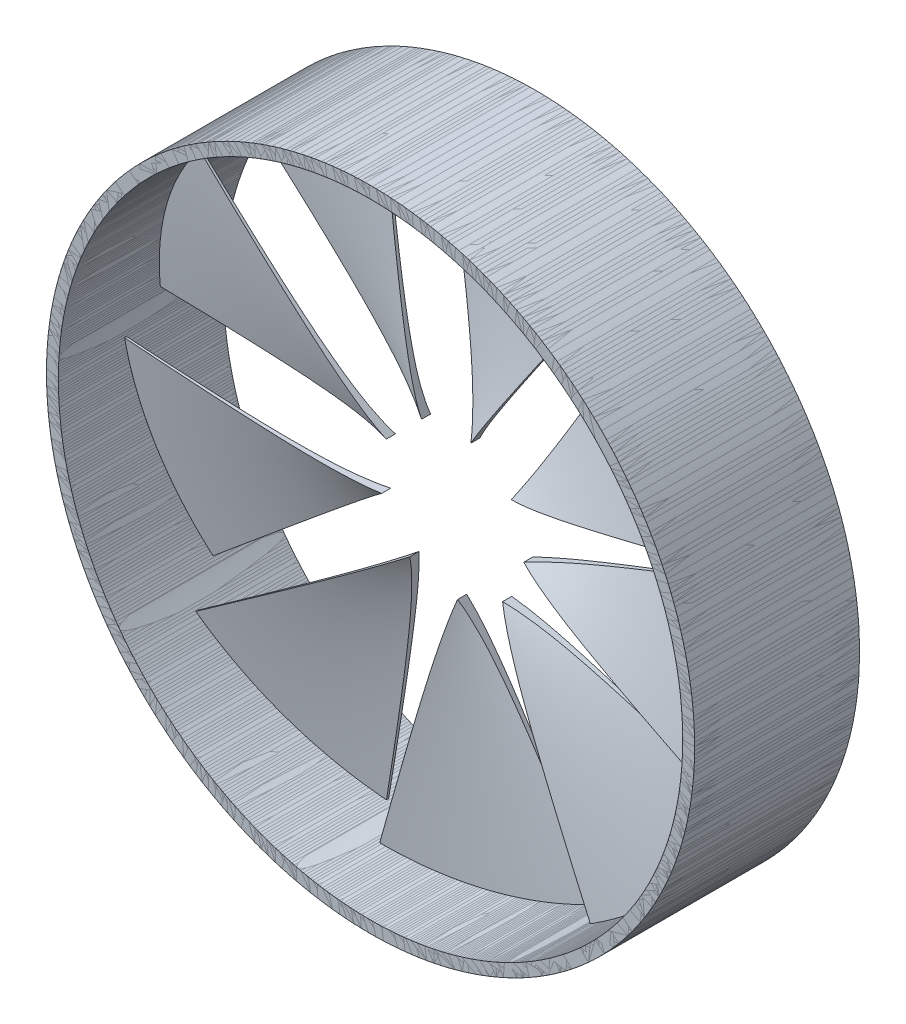
SolidWorks part; units mm, degrees
ref_plane "Front Plane" through (0, 0, 0) normal (0, 0, 1) x (1, 0, 0)
ref_plane "Top Plane" through (0, 0, 0) normal (0, 1, 0) x (1, 0, 0)
ref_plane "Right Plane" through (0, 0, 0) normal (1, 0, 0) x (0, 0, -1)
sketch "Sketch1" plane through (0, 0, 0) normal (0, 0, 1) x (1, 0, 0)
  circle A0 centre (0, 0) radius 137.5645
  dimension "D1" = 275.1291
curve "Helix/Spiral1" pitch 150 height 30 radius 137.5645 left hand yes centre (0, 0, 0) axis (0, 0, 1) start towards (-1, 0, 0)
sketch "Sketch2" plane through (0, 0, 0) normal (0, 0, 1) x (1, 0, 0)
  line L1 (-137.5645, 0) -> (-28.89, 0)
  line L2 (-137.5645, 0) -> (-137.5645, 5)
  line L3 (-137.5645, 5) -> (-28.89, 5)
  line L4 (-28.89, 0) -> (-28.89, 5)
  spline S0 degree 3 poles (-137.5645, 0) (-137.5646, 5.7586) (-136.8395, 17.2886) (-133.5938, 34.3006) (-128.2414, 50.7745) (-120.8664, 66.4468) (-111.5854, 81.0715) (-100.5445, 94.4176) (-87.9181, 106.2746) (-73.9046, 116.4558) (-58.7281, 124.7996) (-47.9865, 129.0522) (-42.5098, 130.8317) knots 0 0 0 0 0.1 0.2 0.3 0.4 0.5 0.6 0.7 0.8 0.9 1 1 1 1 construction
  dimension "D3" = 28.89
sweep "Sweep1" add profiles "Sketch2" path "Helix/Spiral1"
ref_plane "Plane1" through (0, 0, 0) normal (0, 0, 1) x (1, 0, 0)
sketch "Sketch9" plane through (0, 0, 0) normal (0, 0, 1) x (1, 0, 0)
  line L0 (-27.777, 13.1653) -> (-104.2926, 89.6808)
  line L1 (-27.777, 13.1653) -> (-136.917, 13.1653)
  arc A0 (-104.2926, 89.6808) -> (-136.917, 13.1653) centre (0, 0) ccw
  dimension "D2" = 45
  dimension "D1" = 137.5485
  dimension "D3" = 109.14
extrude "Cut-Extrude1" cut sketch "Sketch9" along normal blind 40 flip side to cut
sketch "Sketch10" plane through (0, 0, 0) normal (0, 0, 1) x (1, 0, 0)
  circle A0 centre (0, 0) radius 132.5645
  circle A1 centre (0, 0) radius 137.5645
  dimension "D2" = 265.1291
extrude "Boss-Extrude1" add sketch "Sketch10" along normal blind 45 and the other way blind 25
pattern_circular "CirPattern2" count 9 over 360 about axis through (0, 0, -25) along (0, 0, 1) reverse direction yes of bodies 103
equation "\"ThrusterDim\"=160.5mm"
equation "\"hatchHoleDiameter\"=600mm"
equation "\"hullThickness\"=177.1mm"
equation "\"gasketHullInterconnectWidth\"=100mm"
equation "\"collarThickness\"=20mm"
equation "\"hatchTunnelLength\"=200mm"
equation "\"oRingDiameter\"=2mm"
equation "\"boltPatternRadiusInterconnect\"=500mm"
equation "\"interconnectBoltDiameter\"=30mm"
equation "\"hatchShaftDiameter\"=20mm"
equation "\"hatchMinima\"=39.9mm"
equation "\"hullDiameter\"=2240mm"
equation "\"hatchMaxima\"=180mm"
equation "\"bushingFlatHatch\"=15mm"
equation "\"hingePivotDiameter\"=20mm"
equation "\"handleWidth\"=250mm"
equation "\"handleHeight\"=160mm"
equation "\"handleThickness\"=25mm"
equation "\"FrameLength\"=2600mm"
equation "\"FrameMidLength\"=1800mm"
equation "\"TubeOD\"=100mm"
equation "\"FrameBackFlat\"=500mm"
equation "\"TubeWall\"=15.0001mm"
equation "\"TopMemberAngle\"=140deg"
equation "\"FrameHight\"=2500mm"
equation "\"D1@Sketch1\"=\"ThrusterDim\" *2 *0.8571"
equation "\"D2@Sketch10\"=\"ThrusterDim\" *2 *0.8571-10"
equation "\"th\"=16.5237"
equation "\"D3@Sketch2\"=\"ThrusterDim\" *0.18"
equation "\"D1@Sketch9\"=\"ThrusterDim\" *0.857"
equation "\"D3@Sketch9\"=\"ThrusterDim\" *0.68"
